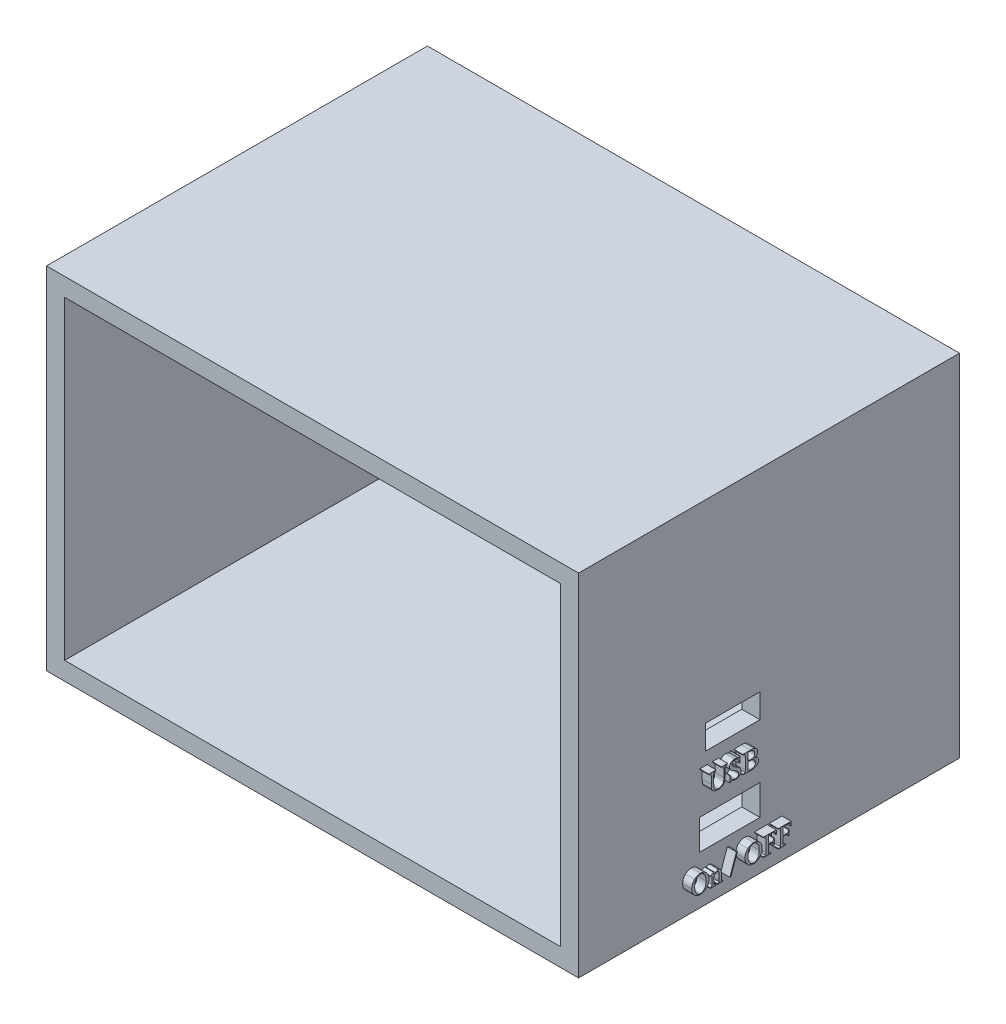
SolidWorks part; units mm, degrees
ref_plane "Front Plane" through (0, 0, 0) normal (0, 0, 1) x (1, 0, 0)
ref_plane "Top Plane" through (0, 0, 0) normal (0, 1, 0) x (1, 0, 0)
ref_plane "Right Plane" through (0, 0, 0) normal (1, 0, 0) x (0, 0, -1)
sketch "Sketch1" plane through (0, 0, 0) normal (0, 0, 1) x (1, 0, 0)
  line L1 (-44, 29) -> (44, 29)
  line L2 (-44, 29) -> (-44, -29)
  line L3 (-44, -29) -> (44, -29)
  line L4 (44, 29) -> (44, -29)
  line L5 (-44, 29) -> (44, -29) construction
  line L6 (-44, -29) -> (44, 29) construction
  line L7 (-41, 26) -> (41, 26)
  line L8 (-41, 26) -> (-41, -26)
  line L9 (-41, -26) -> (41, -26)
  line L10 (41, 26) -> (41, -26)
  line L11 (-41, 26) -> (41, -26) construction
  line L12 (-41, -26) -> (41, 26) construction
  point P0 (0, 0)
  point P5 (0, 0)
  dimension "D1" = 88
  dimension "D2" = 58
  dimension "D3" = 82
  dimension "D4" = 52
extrude "Boss-Extrude1" add sketch "Sketch1" along normal blind 60
sketch "Sketch2" plane through (0, 0, 0) normal (0, 0, -1) x (-1, 0, 0)
  line L1 (-44, 29) -> (44, 29)
  line L2 (-44, 29) -> (-44, -29)
  line L3 (-44, -29) -> (44, -29)
  line L4 (44, 29) -> (44, -29)
  line L5 (-44, 29) -> (44, -29) construction
  line L6 (-44, -29) -> (44, 29) construction
  point P0 (0, 0)
extrude "Boss-Extrude2" add sketch "Sketch2" along normal blind 3
sketch "Sketch3" plane through (44, 0, 0) normal (1, 0, 0) x (0, 0, -1)
  line L0 (-60, -29) -> (-60, 29) construction
  line L1 (-40, -21) -> (-30, -21)
  line L2 (-40, -21) -> (-40, -16)
  line L3 (-40, -16) -> (-30, -16)
  line L4 (-30, -21) -> (-30, -16)
  line L5 (-60, -29) -> (3, -29) construction
  line L7 (-39, -7) -> (-30, -7)
  line L8 (-39, -7) -> (-39, -3)
  line L9 (-39, -3) -> (-30, -3)
  line L10 (-30, -7) -> (-30, -3)
  dimension "D1" = 10
  dimension "D2" = 5
  dimension "D3" = 20
  dimension "D4" = 8
  dimension "D5" = 4
  dimension "D6" = 9
  dimension "D7" = 21
  dimension "D8" = 9
extrude "Cut-Extrude1" cut sketch "Sketch3" against normal blind 8
sketch "Sketch4" plane through (0, 0, -3) normal (0, 0, -1) x (-1, 0, 0)
  line L1 (44, -29) -> (44, 29) construction
  circle A0 centre (19, 0) radius 11.5
  point P5 (0, 0)
  dimension "D1" = 23
  dimension "D2" = 25
extrude "Cut-Extrude2" cut sketch "Sketch4" against normal blind 8
sketch "Sketch5" plane through (0, -29, 0) normal (0, -1, 0) x (1, 0, 0)
  text T0 "Digital Stethoscope" font "Times New Roman" height in points 18
extrude "Boss-Extrude3" add sketch "Sketch5" along normal blind 1.5
sketch "Sketch6" plane through (44, 0, 0) normal (1, 0, 0) x (0, 0, -1)
  line L0 (-39, -7) -> (-30, -7) construction
  line L2 (-39, -3) -> (-39, -7) construction
  text T0 "On / OFF" font "Times New Roman" height in points 12
  text T1 "USB" font "Times New Roman" height in points 12
  dimension "D1" = 5
  dimension "D2" = 1
extrude "Boss-Extrude4" add sketch "Sketch6" along normal blind 1.5
